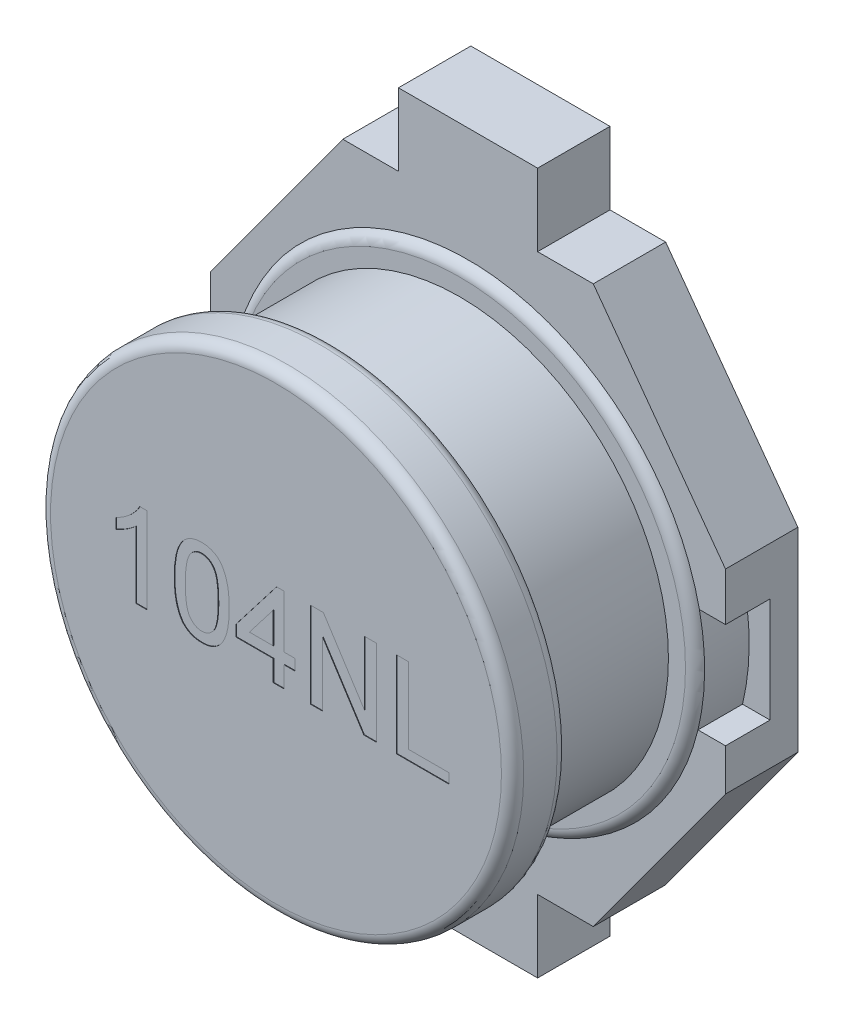
SolidWorks part; units mm, degrees
ref_plane "Plan de face" through (0, 0, 0) normal (0, 0, 1) x (1, 0, 0)
ref_plane "Plan de dessus" through (0, 0, 0) normal (0, 1, 0) x (1, 0, 0)
ref_plane "Plan de droite" through (0, 0, 0) normal (1, 0, 0) x (0, 0, -1)
sketch "Esquisse1" plane through (0, 0, 0) normal (0, 0, 1) x (1, 0, 0)
  line L0 (-2.25, 5) -> (2.25, 5)
  line L1 (-2.25, 5) -> (-4.625, 1.75)
  line L2 (-4.625, 1.75) -> (-4.625, -1.75)
  line L3 (-2.25, -5) -> (2.25, -5)
  line L4 (4.625, 1.75) -> (4.625, -1.75)
  line L5 (2.25, 5) -> (4.625, 1.75)
  line L6 (-2.25, -5) -> (-4.625, -1.75)
  line L7 (2.25, -5) -> (4.625, -1.75)
  dimension "D1" = 9.25
  dimension "D2" = 4.625
  dimension "D3" = 3.5
  dimension "D4" = 3.5
  dimension "D5" = 10
  dimension "D6" = 4.5
  dimension "D7" = 5
extrude "Extrusion1" add sketch "Esquisse1" along normal blind 1.3
sketch "Esquisse2" plane through (0, 0, 0) normal (0, 0, 1) x (1, 0, 0)
  circle A0 centre (0, 0) radius 4.25
extrude "Extrusion2" add sketch "Esquisse2" along normal blind 1.45
sketch "Esquisse3" plane through (0, 0, 1.45) normal (0, 0, 1) x (1, 0, 0)
  circle A0 centre (0, 0) radius 3.75
extrude "Extrusion3" add sketch "Esquisse3" along normal blind 2.3
sketch "Esquisse4" plane through (0, 0, 3.75) normal (0, 0, 1) x (1, 0, 0)
  circle A0 centre (0, 0) radius 4.25
extrude "Extrusion4" add sketch "Esquisse4" along normal blind 1
fillet "Congé1" radius 0.2 2 edges at (4.25, 0, 3.75) (4.25, 0, 4.75)
fillet "Congé2" radius 0.2 1 edges at (4.25, 0, 1.45)
sketch "Esquisse5" plane through (0, 0, 1.3) normal (0, 0, 1) x (1, 0, 0)
  line L0 (-4.625, 1.75) -> (-4.625, -1.75) construction
  line L1 (-4.625, 0.8859) -> (-3.8053, 0.8859)
  line L2 (-4.625, 0.8859) -> (-4.625, -0.9995)
  line L3 (-4.625, -0.9995) -> (-3.8053, -0.9995)
  line L4 (-3.8053, 0.8859) -> (-3.8053, -0.9995)
  line M1 (-4.625, 1.75) -> (-4.625, -1.75)
  circle M9 centre (0, 0) radius 4.25
extrude "Enlèv. mat.-Extru.1" cut sketch "Esquisse5" against normal blind 0.8 contours L3 L1 M1 M9
sketch "Esquisse6" plane through (0, 0, 1.3) normal (0, 0, 1) x (1, 0, 0)
  line L0 (4.625, -1.75) -> (4.625, 1.75) construction
  line L1 (3.6951, 0.8859) -> (4.625, 0.8859)
  line L2 (3.6951, 0.8859) -> (3.6951, -0.9995)
  line L3 (3.6951, -0.9995) -> (4.625, -0.9995)
  line L4 (4.625, 0.8859) -> (4.625, -0.9995)
  line L5 (-4.625, -0.9995) -> (-4.1308, -0.9995) construction
  line L6 (-4.625, 0.8859) -> (-4.1566, 0.8859) construction
  arc M3 (-4.1566, 0.8859) -> (-4.1308, -0.9995) centre (0, 0) cw
  line M9 (4.625, -1.75) -> (4.625, 1.75)
extrude "Enlèv. mat.-Extru.3" cut sketch "Esquisse6" against normal blind 0.8 contours L3 L1 M3 M9
sketch "Esquisse8" plane through (0, 5, 0) normal (0, 1, 0) x (1, 0, 0)
  line L0 (2.25, 0) -> (-2.25, 0) construction
  line L1 (-1.25, 0) -> (1.25, 0)
  line L2 (-1.25, 0) -> (-1.25, -1.3)
  line L3 (-1.25, -1.3) -> (1.25, -1.3)
  line L4 (1.25, 0) -> (1.25, -1.3)
  line L5 (2.25, -1.3) -> (-2.25, -1.3) construction
  dimension "D1" = 1.25
  dimension "D2" = 1.25
extrude "Extrusion5" add sketch "Esquisse8" along normal blind 1.3
sketch "Esquisse9" plane through (0, -5, 0) normal (0, -1, 0) x (1, 0, 0)
  line L0 (-2.25, 0) -> (2.25, 0) construction
  line L1 (1.25, 0) -> (-1.25, 0)
  line L2 (1.25, 0) -> (1.25, 1.3)
  line L3 (1.25, 1.3) -> (-1.25, 1.3)
  line L4 (-1.25, 0) -> (-1.25, 1.3)
  line L5 (-2.25, 1.3) -> (2.25, 1.3) construction
  dimension "D1" = 1.25
  dimension "D2" = 1.25
extrude "Extrusion6" add sketch "Esquisse9" along normal blind 1.3
sketch "Esquisse10" plane through (0, 0, 4.75) normal (0, 0, 1) x (1, 0, 0)
  text T0 "104NL" font "Arial" height in points 6
extrude "Enlèv. mat.-Extru.4" cut sketch "Esquisse10" against normal blind 0.01
